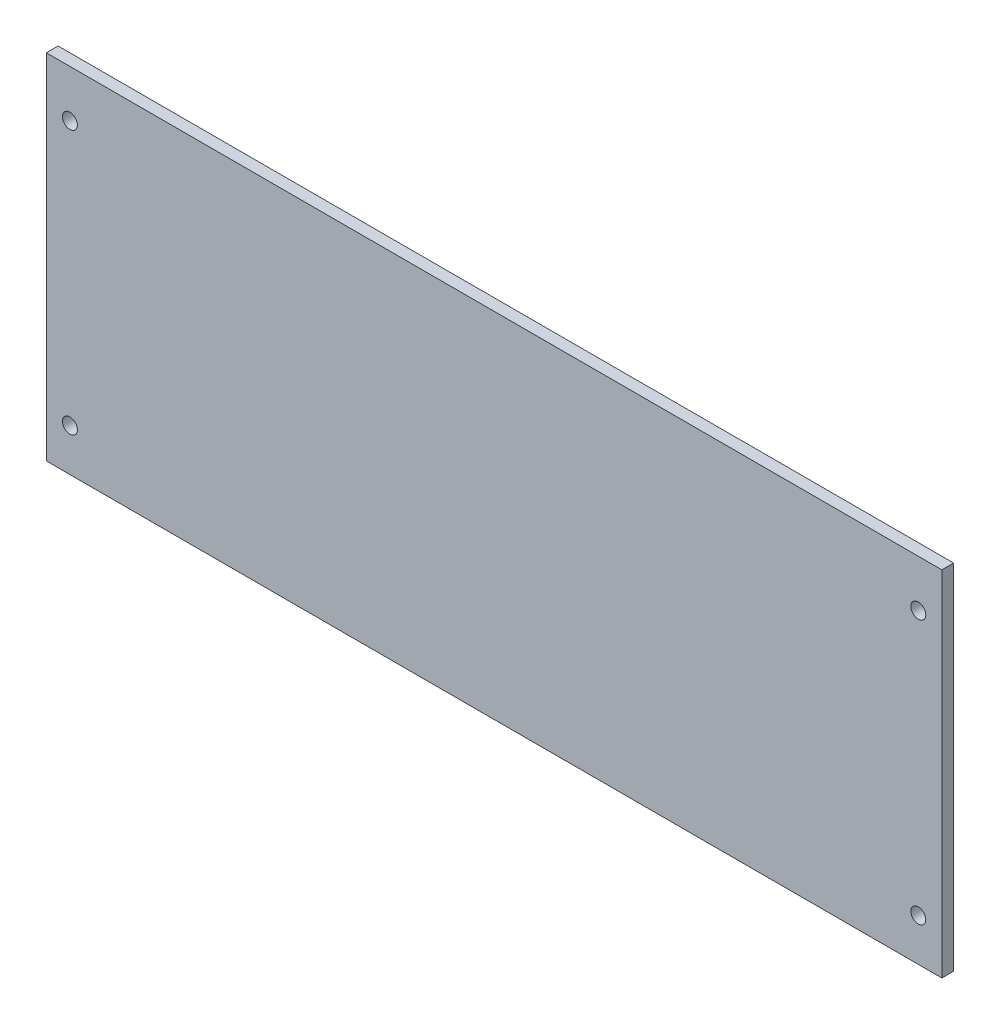
SolidWorks part; units mm, degrees
ref_plane "Alzado" through (0, 0, 0) normal (0, 0, 1) x (1, 0, 0)
ref_plane "Planta" through (0, 0, 0) normal (0, 1, 0) x (1, 0, 0)
ref_plane "Vista lateral" through (0, 0, 0) normal (1, 0, 0) x (0, 0, -1)
sketch "Sketch1" plane through (0, 0, 0) normal (0, 0, 1) x (1, 0, 0)
  line L1 (0, 0) -> (190, 0)
  line L2 (0, 0) -> (0, 75)
  line L3 (0, 75) -> (190, 75)
  line L4 (190, 0) -> (190, 75)
  circle A0 centre (5, 65) radius 1.585
  circle A1 centre (185, 65) radius 1.585
  circle A2 centre (5, 9) radius 1.585
  circle A3 centre (185, 9) radius 1.585
  dimension "D3" = 3.17
  dimension "D4" = 3.17
  dimension "D10" = 3.17
  dimension "D14" = 3.17
  dimension "D1" = 75
  dimension "190" = 190
  dimension "D2" = 5
  dimension "D5" = 5
  dimension "D6" = 10
  dimension "D7" = 10
  dimension "D8" = 180
  dimension "D9" = 56
  dimension "D11" = 5
  dimension "D12" = 9
  dimension "D13" = 9
  dimension "D15" = 5
extrude "Boss-Extrude1" add sketch "Sketch1" along normal blind 2.5
equation "\"0.5.00mm\"=1"
